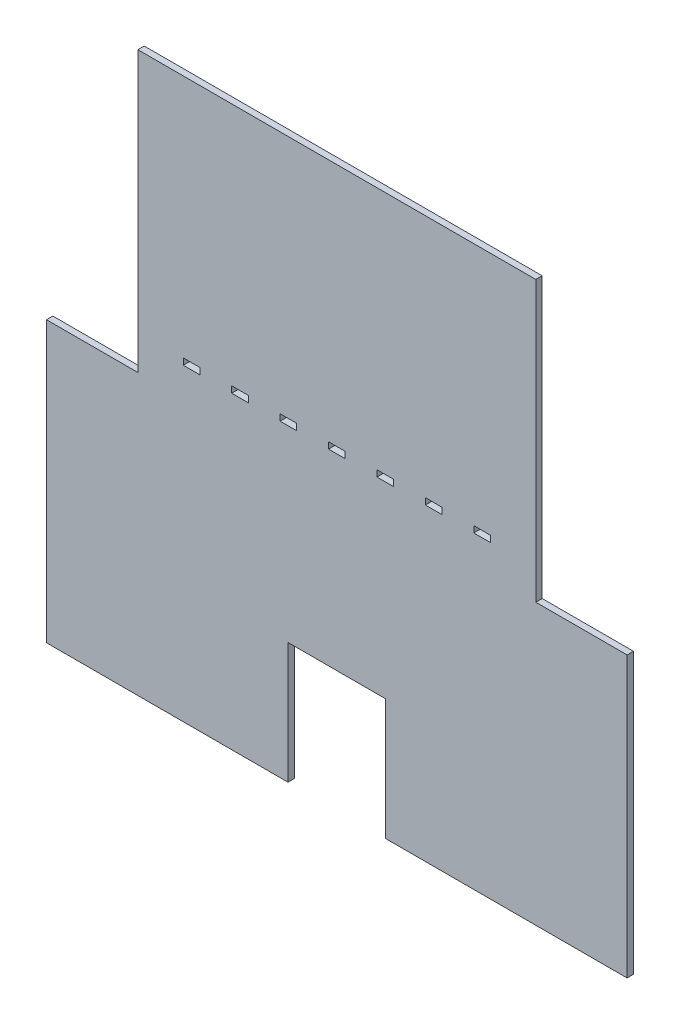
SolidWorks part; units mm, degrees
material "Oak"
ref_plane "Front Plane" through (0, 0, 0) normal (0, 0, 1) x (1, 0, 0)
ref_plane "Top Plane" through (0, 0, 0) normal (0, 1, 0) x (1, 0, 0)
ref_plane "Right Plane" through (0, 0, 0) normal (1, 0, 0) x (0, 0, -1)
sketch "Sketch1" plane through (0, 0, 0) normal (0, 0, 1) x (1, 0, 0)
  line L1 (0, 0) -> (273.4, 0)
  line L2 (0, 0) -> (0, -263.4)
  line L3 (0, -263.4) -> (273.4, -263.4)
  line L4 (273.4, 0) -> (273.4, -263.4)
  dimension "D1" = 273.4
  dimension "D2" = 263.4
extrude "Boss-Extrude1" add sketch "Sketch1" along normal blind 3
sketch "Sketch2" plane through (0, 0, 3) normal (0, 0, 1) x (1, 0, 0)
  line L1 (0, 0) -> (43, 0)
  line L2 (0, 0) -> (0, -131.64)
  line L3 (0, -131.64) -> (43, -131.64)
  line L4 (43, 0) -> (43, -131.64)
  line L9 (273.4, 0) -> (230.4, 0)
  line L10 (273.4, 0) -> (273.4, -131.64)
  line L11 (273.4, -131.64) -> (230.4, -131.64)
  line L12 (230.4, 0) -> (230.4, -131.64)
  dimension "D1" = 43
  dimension "D2" = 131.64
  dimension "D5" = 43
  dimension "D6" = 131.64
extrude "Cut-Extrude1" cut sketch "Sketch2" against normal through all
sketch "Sketch3" plane through (0, 0, 0) normal (0, 0, -1) x (-1, 0, 0)
  line L0 (0, -263.4) -> (-273.4, -263.4) construction
  line L1 (-159.7, -206.4) -> (-113.7, -206.4)
  line L2 (-159.7, -206.4) -> (-159.7, -263.4)
  line L3 (-159.7, -263.4) -> (-113.7, -263.4)
  line L4 (-113.7, -206.4) -> (-113.7, -263.4)
  line L5 (-273.4, -263.4) -> (-273.4, -131.64) construction
  dimension "D1" = 46
  dimension "D2" = 57
  dimension "D3" = 113.7
extrude "Cut-Extrude2" cut sketch "Sketch3" against normal through all
sketch "Sketch5" plane through (0, 0, 0) normal (0, 0, -1) x (-1, 0, 0)
  line L1 (-140.6, -115) -> (-132.8, -115)
  line L2 (-140.6, -115) -> (-140.6, -118)
  line L3 (-140.6, -118) -> (-132.8, -118)
  line L4 (-132.8, -115) -> (-132.8, -118)
  line L5 (-273.4, -263.4) -> (-273.4, -131.64) construction
  line L6 (-230.4, 0) -> (-43, 0) construction
  dimension "D1" = 7.8
  dimension "D2" = 3
  dimension "D3" = 132.8
  dimension "D4" = 115
extrude "Cut-Extrude3" cut sketch "Sketch5" against normal through all
pattern_linear "LPattern2" count 4 spacing 22.8 along (1, 0, 0) count 4 spacing 22.8 along (-1, 0, 0) of "Cut-Extrude3"
